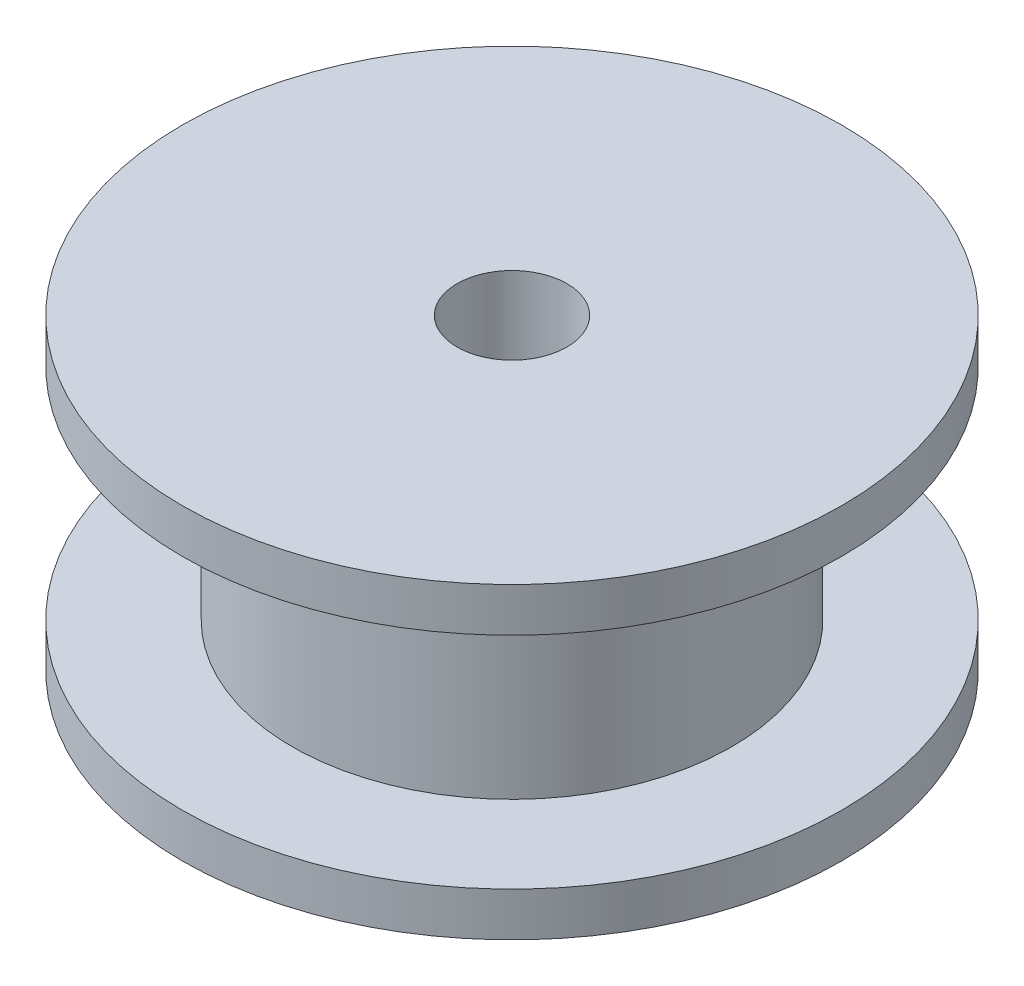
SolidWorks part; units mm, degrees
material "AISI 1020"
ref_plane "Front Plane" through (0, 0, 0) normal (0, 0, 1) x (1, 0, 0)
ref_plane "Top Plane" through (0, 0, 0) normal (0, 1, 0) x (1, 0, 0)
ref_plane "Right Plane" through (0, 0, 0) normal (1, 0, 0) x (0, 0, -1)
sketch "Sketch1" plane through (0, 0, 0) normal (1, 0, 0) x (0, 0, -1)
  line L0 (0, 0) -> (0, 2.8) construction
  line L1 (0, 2.8) -> (-0.5, 2.8) construction
  line L2 (-3, 2.8) -> (-0.5, 2.8)
  line L3 (-0.5, 2.8) -> (-0.5, 0)
  line L4 (-0.5, 0) -> (-3, 0)
  line L5 (-3, 0) -> (-3, 0.4)
  line L6 (-3, 0.4) -> (-2, 0.4)
  line L7 (-2, 0.4) -> (-2, 2.4)
  line L8 (-2, 2.4) -> (-3, 2.4)
  line L9 (-3, 2.4) -> (-3, 2.8)
  dimension "D1" = 0.5
  dimension "D2" = 2.8
  dimension "D3" = 0.4
  dimension "D4" = 2.5
  dimension "D5" = 1.5
  dimension "D6" = 2
revolve "Revolve1" add sketch "Sketch1" angle 360 about L0
ref_axis "Axis1" through (0, -0.14, 0) along (0, 1, 0)
